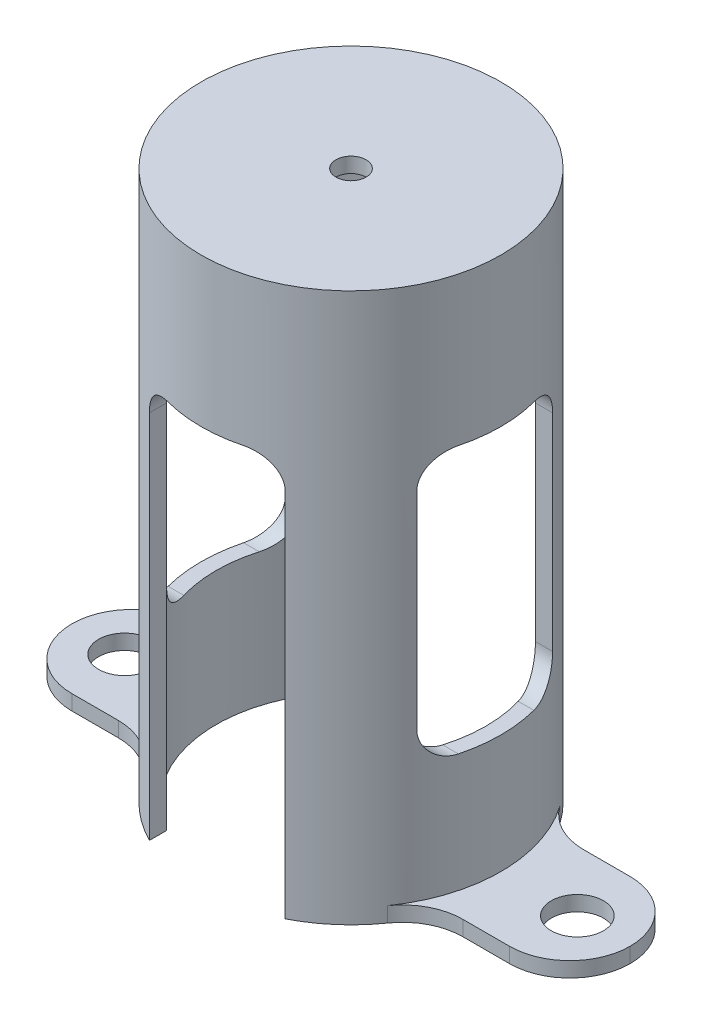
SolidWorks part; units mm, degrees
material "6061-T6 (SS)"
ref_plane "Front Plane" through (0, 0, 0) normal (0, 0, 1) x (1, 0, 0)
ref_plane "Top Plane" through (0, 0, 0) normal (0, 1, 0) x (1, 0, 0)
ref_plane "Right Plane" through (0, 0, 0) normal (1, 0, 0) x (0, 0, -1)
sketch "Sketch2" plane through (0, 0, 0) normal (0, 1, 0) x (1, 0, 0)
  circle A1 centre (0, 0) radius 9.9375
  dimension "D2" = 19.875
extrude "Boss-Extrude1" add sketch "Sketch2" along normal blind 35.384
sketch "Sketch4" plane through (0, 35.384, 0) normal (0, 1, 0) x (1, 0, 0)
  circle A0 centre (0, 0) radius 1
  dimension "D1" = 2
extrude "Cut-Extrude2" cut sketch "Sketch4" against normal through all
sketch "Sketch11" plane through (0, 0, 0) normal (0, -1, 0) x (1, 0, 0)
  line L0 (9.0969, 4) -> (18.5, 4)
  line L1 (-18.5, 4) -> (-9.0969, 4)
  line L2 (-18.5, 4) -> (-18.5, -4)
  line L3 (-18.5, -4) -> (-9.0969, -4)
  line L4 (18.5, 4) -> (18.5, -4)
  line L5 (-18.5, 4) -> (18.5, -4) construction
  line L6 (-18.5, -4) -> (18.5, 4) construction
  line L7 (9.0969, -4) -> (18.5, -4)
  arc A0 (9.0969, 4) -> (-9.0969, 4) centre (0, 0) ccw
  circle A1 centre (0, 0) radius 8.9375
  arc A2 (-9.0969, -4) -> (9.0969, -4) centre (0, 0) ccw
  point P0 (0, 0)
  dimension "D3" = 19.875
  dimension "D4" = 17.875
  dimension "D1" = 8
  dimension "D2" = 37
extrude "Boss-Extrude2" add sketch "Sketch11" along normal blind 1
sketch "Sketch12" plane through (0, 0, 0) normal (0, -1, 0) x (1, 0, 0)
  circle A0 centre (0, 0) radius 8.9375
  dimension "D1" = 17.875
extrude "Cut-Extrude7" cut sketch "Sketch12" against normal blind 34.384
ref_plane "Plane4" through (0, 0, 30) normal (0, 0, 1) x (1, 0, 0)
sketch "Sketch13" plane through (0, 0, 30) normal (0, 0, 1) x (1, 0, 0)
  line L0 (0, -10.9313) -> (0, 10.9313) construction
  line L1 (-4.5, 25.538) -> (4.5, 25.538)
  line L2 (-4.5, 25.538) -> (-4.5, -1)
  line L3 (-4.5, -1) -> (4.5, -1)
  line L4 (4.5, 25.538) -> (4.5, -1)
  line L5 (-4.5, 25.538) -> (4.5, -1) construction
  line L6 (-4.5, -1) -> (4.5, 25.538) construction
  line L7 (-9.0969, -1) -> (9.0969, -1) construction
  point P0 (0, 12.269)
  dimension "D1" = 26.538
  dimension "D2" = 9
extrude "Cut-Extrude8" cut sketch "Sketch13" against normal through all
ref_plane "Plane5" through (30, 0, 0) normal (1, 0, 0) x (0, 0, -1)
sketch "Sketch14" plane through (30, 0, 0) normal (1, 0, 0) x (0, 0, -1)
  line L0 (0, 10.9313) -> (0, -10.9313) construction
  line L1 (-4.5, 25.538) -> (4.5, 25.538)
  line L2 (-4.5, 25.538) -> (-4.5, 7.846)
  line L3 (-4.5, 7.846) -> (4.5, 7.846)
  line L4 (4.5, 25.538) -> (4.5, 7.846)
  line L5 (-4.5, 25.538) -> (4.5, 7.846) construction
  line L6 (-4.5, 7.846) -> (4.5, 25.538) construction
  line L7 (4, -1) -> (-4, -1) construction
  point P0 (0, 16.692)
  dimension "D2" = 9
  dimension "D1" = 17.692
  dimension "D3" = 17.692
extrude "Cut-Extrude9" cut sketch "Sketch14" against normal through all
fillet "Fillet3" radius 2 12 edges at (4.5, 25.538, -8.2911) (-4.5, 25.538, -8.2911) (-4.5, 25.538, 8.2911) (4.5, 25.538, 8.2911) (-8.2911, 25.538, 4.5) (-8.2911, 25.538, -4.5) (-8.2911, 7.846, -4.5) (-8.2911, 7.846, 4.5) (8.2911, 7.846, 4.5) (8.2911, 25.538, 4.5) (8.2911, 25.538, -4.5) (8.2911, 7.846, -4.5)
fillet "Fillet4" radius 4 8 edges at (9.0969, -0.5, -4) (18.5, -0.5, -4) (9.0969, -0.5, 4) (18.5, -0.5, 4) (-9.0969, -0.5, 4) (-18.5, -0.5, -4) (-9.0969, -0.5, -4) (-18.5, -0.5, 4)
sketch "Sketch15" plane through (0, 0, 0) normal (0, 1, 0) x (1, 0, 0)
  line L0 (-20.0112, 0) -> (20.0112, 0) construction
  circle A0 centre (-15, 0) radius 1.7272
  circle A1 centre (15, 0) radius 1.7272
  dimension "D3" = 3.4544
  dimension "D4" = 3.4544
  dimension "D1" = 15
  dimension "D2" = 15
extrude "Cut-Extrude10" cut sketch "Sketch15" against normal up to next
equation "\"FrangiboltTotalDiameter\"= 0.625in"
equation "\"FrangiboltTotalLength\"= 0.960in"
equation "\"FrangiboltThruHoleDiameter\"= 0.169in"
equation "\"EnclosureWallThickness\"= 1mm"
equation "\"EnclosureWallSpacing\"= 1mm"
equation "\"EnclosureInnerDiameter\"= \"FrangiboltTotalDiameter\" + 2 * \"EnclosureWallSpacing\""
equation "\"EnclosureOuterDiameter\"= \"FrangiboltTotalDiameter\" + 2 * \"EnclosureWallSpacing\" + 2 * \"EnclosureWallThickness\""
equation "\"EnclosureTotalLength\"= \"FrangiboltTotalLength\" + \"DamperLength\" + \"EnclosureWallThickness\""
equation "\"D2@Sketch2\"=\"EnclosureOuterDiameter\""
equation "\"D1@Boss-Extrude1\"=\"EnclosureTotalLength\""
equation "\"DamperLength\"= 10mm"
equation "\"EnclosureLip\"= 5mm"
equation "\"FrangiboltBoxWidth\"= 7mm"
equation "\"EnclosureMountingStandoff\"= 37mm"
equation "\"D2@Sketch11\"=\"EnclosureMountingStandoff\""
equation "\"D3@Sketch11\"=\"EnclosureOuterDiameter\""
equation "\"D4@Sketch11\"=\"EnclosureInnerDiameter\""
equation "\"D1@Boss-Extrude2\"=\"EnclosureWallThickness\""
equation "\"D1@Sketch12\"=\"EnclosureInnerDiameter\""
equation "\"D1@Cut-Extrude7\"=\"EnclosureTotalLength\"-\"EnclosureWallThickness\""
equation "\"D1@Sketch13\"=\"EnclosureTotalLength\"*0.75"
equation "\"D2@Sketch13\"=\"FrangiboltBoxWidth\"+2mm"
equation "\"D1@Sketch14\"=\"EnclosureTotalLength\"*0.5"
equation "\"D2@Sketch14\"=\"FrangiboltBoxWidth\"+2mm"
equation "\"D3@Sketch14\"=\"EnclosureTotalLength\"*0.5"
equation "\"EnclosureMountingHoleDiameter\"= 0.1360in'#29 Tap Drill"
equation "\"D3@Sketch15\"=\"EnclosureMountingHoleDiameter\""
equation "\"D4@Sketch15\"=\"EnclosureMountingHoleDiameter\""
